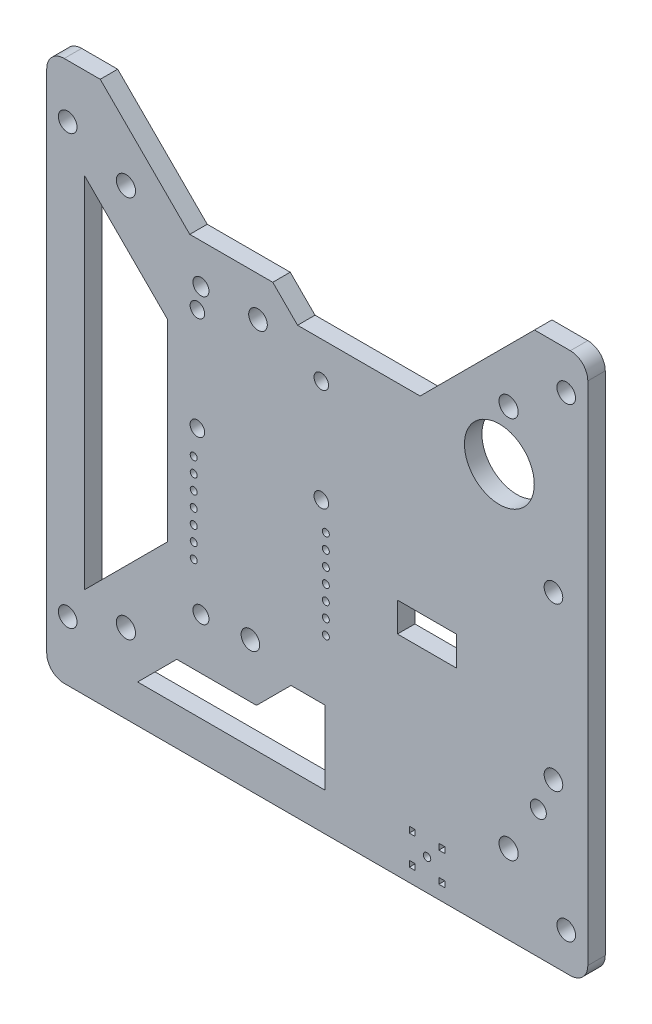
SolidWorks part; units mm, degrees
note: The reader was unsure of these and kept them because the rebuilt part matched: shared geometry of "Sketch2<3>".
ref_plane "Front Plane" through (0, 0, 0) normal (0, 0, 1) x (1, 0, 0)
ref_plane "Top Plane" through (0, 0, 0) normal (0, 1, 0) x (1, 0, 0)
ref_plane "Right Plane" through (0, 0, 0) normal (1, 0, 0) x (0, 0, -1)
sketch "Sketch1" plane through (0, 0, 0) normal (0, 0, 1) x (1, 0, 0)
  line L1 (-46.4872, 46.5) -> (46.4872, 46.5)
  line L2 (-46.4872, 46.5) -> (-46.4872, -46.5)
  line L3 (-46.4872, -46.5) -> (46.4872, -46.5)
  line L4 (46.4872, 46.5) -> (46.4872, -46.5)
  line L5 (-46.4872, 46.5) -> (46.4872, -46.5) construction
  line L6 (-46.4872, -46.5) -> (46.4872, 46.5) construction
  point P0 (0, 0)
  dimension "D1" = 93
  dimension "D2" = 92.9743
extrude "Boss-Extrude1" add sketch "Sketch1" along normal blind 3
fillet "Fillet1" radius 3 4 edges at (-46.4872, -46.5, 1.5) (46.4872, -46.5, 1.5) (46.4872, 46.5, 1.5) (-46.4872, 46.5, 1.5)
sketch "Sketch2" plane through (0, 0, 3) normal (0, 0, 1) x (1, 0, 0)
  line L4 (-39.9872, -30.8076) -> (-39.9872, 30.8076)
  line L5 (-39.9872, 30.8076) -> (-25.7221, 16.5425)
  line L6 (-25.7221, -16.5425) -> (-39.9872, -30.8076)
  line L7 (-43.4872, -46.5) -> (43.4872, -46.5) construction
  line L8 (-39.9872, 40) -> (-39.9872, -40)
  line L9 (-39.9872, -40) -> (39.9872, -40)
  line L10 (39.9872, -40) -> (39.9872, 40)
  line L11 (39.9872, 40) -> (-39.9872, 40)
  line L12 (-39.9872, 30.8076) -> (-39.9872, -40)
  line L16 (-30.8716, -39.9778) -> (-24.14, -33.2462)
  line L17 (-24.14, -33.2462) -> (-10.44, -33.2462)
  line L18 (-10.44, -33.2462) -> (-4.5144, -27.3206)
  line L23 (1.3289, -39.9776) -> (-30.8716, -39.9778)
  line L40 (-37.2952, 46.5) -> (-21.9085, 31.1134)
  line L41 (43.4872, 46.5) -> (-43.4872, 46.5) construction
  line L42 (-21.9085, 31.1134) -> (-7.6485, 31.1134)
  line L43 (-7.6485, 31.1134) -> (-3.3847, 26.8495)
  line L47 (17.6744, 26.8495) -> (37.3248, 46.5)
  line L48 (37.3248, 46.5) -> (-37.2952, 46.5)
  line L59 (1.3289, -27.3206) -> (1.3289, -39.9776)
  line L60 (-25.7221, 16.5425) -> (-25.7221, -16.5425)
  line L61 (-3.3847, 26.8495) -> (17.6744, 26.8495)
  line L62 (-4.5144, -27.3206) -> (1.3289, -27.3206)
  line L63 (26.4872, -45.5) -> (26.4872, -4.5)
  line L64 (26.4872, -4.5) -> (11.2372, -4.5)
  line L66 (32.3931, 23.4364) -> (32.3931, 3.3224)
  line L67 (32.3931, 3.3224) -> (42.3602, 3.3224)
  line L68 (42.3602, 23.4364) -> (42.3602, 3.3224)
  line L70 (11.2372, -4.5) -> (11.2372, -45.5)
  line L71 (11.2372, -45.5) -> (26.4872, -45.5)
  line L72 (13.7772, -5.47) -> (23.9472, -5.47)
  line L73 (18.8622, -45.5) -> (18.8622, -34.8796)
  line L74 (13.7772, -10.52) -> (23.9472, -10.52)
  line L75 (16.8322, -41.15) -> (21.1585, -41.15)
  line L76 (15.8122, -43.18) -> (16.8322, -43.18)
  line L77 (15.8122, -43.18) -> (15.8122, -44.2)
  line L78 (23.9472, -5.47) -> (23.9472, -10.52)
  line L79 (13.7772, -5.47) -> (13.7772, -10.52)
  line L80 (15.8122, -44.2) -> (16.8322, -44.2)
  line L81 (16.8322, -43.18) -> (16.8322, -44.2)
  line L82 (15.8122, -38.1) -> (16.8322, -38.1)
  line L83 (16.8322, -39.12) -> (16.8322, -38.1)
  line L84 (15.8122, -39.12) -> (16.8322, -39.12)
  line L85 (15.8122, -39.12) -> (15.8122, -38.1)
  line L86 (21.9122, -44.2) -> (20.8922, -44.2)
  line L87 (20.8922, -43.18) -> (20.8922, -44.2)
  line L88 (21.9122, -43.18) -> (20.8922, -43.18)
  line L89 (21.9122, -43.18) -> (21.9122, -44.2)
  line L90 (21.9122, -39.12) -> (21.9122, -38.1)
  line L91 (21.9122, -39.12) -> (20.8922, -39.12)
  line L92 (20.8922, -39.12) -> (20.8922, -38.1)
  line L93 (21.9122, -38.1) -> (20.8922, -38.1)
  line L95 (46.4872, -43.5) -> (46.4872, 43.5) construction
  line L96 (32.3931, 23.4364) -> (42.3602, 23.4364)
  circle A0 centre (18.8622, -41.15) radius 0.64
  point P29 (-27.5058, -36.612)
  point P60 (18.8622, -41.15)
  dimension "D23" = 1
  dimension "D2" = 15.6924
  dimension "D3" = 61.6152
  dimension "D4" = 41
  dimension "D5" = 15.25
  dimension "D6" = 74.62
  dimension "D7" = 6.192
  dimension "D8" = 0.97
  dimension "D9" = 9.52
  dimension "D10" = 13.7
  dimension "D11" = 8.38
  dimension "D12" = 1.02
  dimension "D13" = 5.05
  dimension "D14" = 21.76
  dimension "D15" = 12.93
  dimension "D16" = 14.26
  dimension "D17" = 1.02
  dimension "D18" = 2.03
  dimension "D19" = 4.35
  dimension "D20" = 2.03
  dimension "D21" = 2.54
  dimension "D22" = 20
  dimension "D25" = 6.03
  dimension "D1" = 6.5
extrude "Cut-Extrude1" cut sketch "Sketch2" against normal blind 3
sketch "Sketch3" plane through (0, 0, 3) normal (0, 0, 1) x (1, 0, 0)
  line L0 (-37.2952, 46.5) -> (-43.4872, 46.5) construction
  line L1 (-46.4872, 43.5) -> (-46.4872, -43.5) construction
  circle A0 centre (-42.8872, 37.38) radius 1.6
  circle A1 centre (-32.8772, 32.89) radius 1.65
  circle A2 centre (-19.9872, 24.3) radius 1.375
  circle A3 centre (-10.1872, 24.3) radius 1.6
  point P0 (-42.8872, 37.38)
  point P1 (-32.8772, 32.89)
  point P2 (-19.9872, 24.3)
  point P3 (-10.1872, 24.3)
  dimension "D1" = 9.12
  dimension "D2" = 3.6
  dimension "D3" = 13.61
  dimension "D4" = 13.61
  dimension "D5" = 22.2
  dimension "D6" = 26.5
  dimension "D7" = 36.3
  dimension "D8" = 22.2
extrude "Cut-Extrude2" cut sketch "Sketch3" against normal blind 3
sketch "Sketch4" plane through (0, 0, 3) normal (0, 0, 1) x (1, 0, 0)
  line L0 (-46.4872, 43.5) -> (-46.4872, -43.5) construction
  line L1 (-43.4872, -46.5) -> (43.4872, -46.5) construction
  line L2 (46.4872, -43.5) -> (46.4872, 43.5) construction
  line L3 (43.4872, 46.5) -> (37.3248, 46.5) construction
  circle A0 centre (42.7772, -40.07) radius 1.6
  circle A1 centre (32.8772, -32.89) radius 1.65
  circle A2 centre (37.9872, -24.5) radius 1.375
  circle A3 centre (40.5872, -18.8) radius 1.6
  circle A4 centre (-42.8872, -36.27) radius 1.6
  circle A5 centre (-32.8772, -32.89) radius 1.65
  circle A6 centre (-19.9872, -24.5) radius 1.375
  circle A7 centre (-11.4872, -24) radius 1.6
  circle A8 centre (42.7772, 39.9) radius 1.6
  circle A9 centre (32.8772, 32.89) radius 1.65
  circle A11 centre (40.5872, 9.1) radius 1.6
  point P0 (-42.8872, -36.27)
  point P1 (-32.8772, -32.89)
  point P2 (-19.9872, -24.5)
  point P3 (-11.4872, -24)
  point P8 (42.7772, -40.07)
  point P9 (32.8772, -32.89)
  point P10 (37.9872, -24.5)
  point P11 (40.5872, -18.8)
  point P30 (42.7772, 39.9)
  point P31 (32.8772, 32.89)
  point P32 (37.9872, 24.5)
  point P33 (40.5872, 9.1)
  point P34 (42.7772, 39.9)
  dimension "D17" = 6.6
  dimension "D1" = 3.6
  dimension "D2" = 13.61
  dimension "D3" = 26.5
  dimension "D4" = 35
  dimension "D5" = 10.23
  dimension "D6" = 13.61
  dimension "D7" = 22
  dimension "D8" = 22.5
  dimension "D9" = 5.9
  dimension "D10" = 27.7
  dimension "D11" = 8.5
  dimension "D12" = 22
  dimension "D13" = 13.61
  dimension "D14" = 13.61
  dimension "D15" = 3.71
  dimension "D16" = 6.43
  dimension "D18" = 3.71
  dimension "D19" = 13.61
  dimension "D20" = 13.61
  dimension "D21" = 8.5
  dimension "D22" = 22
  dimension "D23" = 5.9
  dimension "D24" = 37.4
extrude "Cut-Extrude3" cut sketch "Sketch4" against normal blind 3
sketch "Sketch5" plane through (0, 0, 3) normal (0, 0, 1) x (1, 0, 0)
  line L0 (-22.3787, 22.3) -> (-22.3787, -19.7)
  line L1 (-9.8787, 22.3) -> (-9.8787, -19.7)
  circle A0 centre (-20.5987, 20.56) radius 1.25
  circle A1 centre (0.6913, 20.56) radius 1.25
  circle A2 centre (-20.5987, 2.9) radius 1.25
  circle A3 centre (0.6913, 2.9) radius 1.25
  circle A4 centre (-21.2287, -1.6) radius 0.6
  circle A5 centre (-21.2287, -4.15) radius 0.6
  circle A6 centre (-21.2287, -6.7) radius 0.6
  circle A7 centre (-21.2287, -9.25) radius 0.6
  circle A8 centre (-21.2287, -11.8) radius 0.6
  circle A9 centre (-21.2287, -14.35) radius 0.6
  circle A10 centre (-21.2287, -16.9) radius 0.6
  circle A11 centre (1.4713, -16.9) radius 0.6
  circle A12 centre (1.4713, -14.35) radius 0.6
  circle A13 centre (1.4713, -11.8) radius 0.6
  circle A14 centre (1.4713, -9.25) radius 0.6
  circle A15 centre (1.4713, -4.15) radius 0.6
  circle A16 centre (1.4713, -6.7) radius 0.6
  circle A17 centre (1.4713, -1.6) radius 0.6
  point P0 (-20.5987, 20.56)
  point P1 (0.6913, 20.56)
  point P6 (-22.3787, 22.3)
  point P9 (0.6913, 2.9)
  point P10 (-19.9872, 24.3)
  point P18 (-21.2287, -1.6)
  dimension "D1" = 21.29
  dimension "D6" = 17.66
  dimension "D10" = 7
  dimension "D2" = 42
  dimension "D3" = 0
  dimension "D4" = 2
  dimension "D5" = 1.74
  dimension "D7" = 1.78
  dimension "D8" = 4.5
  dimension "D9" = 1.15
  dimension "D11" = 12.5
extrude "Cut-Extrude4" cut sketch "Sketch5" against normal through all contours A1 | A0 | A3 | A2 | A4 | A5 | A6 | A7 | A8 | A9 | A10 | A17 | A15 | A16 | A14 | A13 | A12 | A11
extrude "Cut-Extrude5" cut sketch "Sketch2<3>" against normal blind 10 contours L72 L79 L74 L78 | L85 L84 L83 L82 | L90 L93 L92 L91 | L75 A0 L73 | L73 A0 L75 | L75 A0 L73 | L73 A0 L75 | L89 L88 L87 L86 | L81 L76 L77 L80
sketch "Sketch2<3>" plane through (0, 0, 3) normal (0, 0, 1) x (1, 0, 0) same geometry as "Sketch2"
sketch "Sketch7" plane through (0, 0, 3) normal (0, 0, 1) x (1, 0, 0)
  line L0 (43.4872, 46.5) -> (37.3248, 46.5) construction
  line L1 (46.4872, -43.5) -> (46.4872, 43.5) construction
  circle A0 centre (31.2872, 23.5) radius 6
  point P0 (31.2872, 23.5)
  dimension "D1" = 23
  dimension "D2" = 15.2
extrude "Cut-Extrude6" cut sketch "Sketch7" against normal through all
